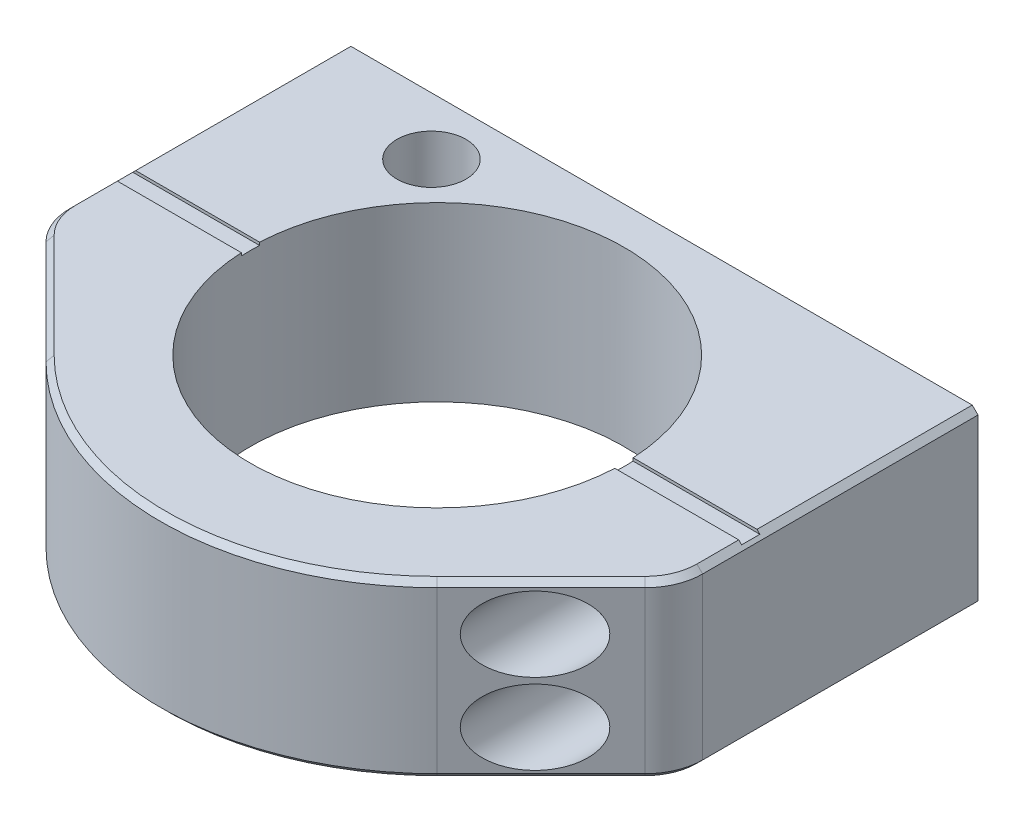
SolidWorks part; units mm, degrees
ref_plane "Front Plane" through (0, 0, 0) normal (0, 0, 1) x (1, 0, 0)
ref_plane "Top Plane" through (0, 0, 0) normal (0, 1, 0) x (1, 0, 0)
ref_plane "Right Plane" through (0, 0, 0) normal (1, 0, 0) x (0, 0, -1)
sketch "Sketch1" plane through (0, 0, 0) normal (0, 1, 0) x (1, 0, 0)
  line L0 (-34, -23) -> (-55, -2)
  line L2 (55, -2) -> (55, 50)
  line L3 (55, 50) -> (-55, 50)
  line L4 (-55, -2) -> (-55, 50)
  line L5 (34, -23) -> (55, -2)
  circle A0 centre (0, 11) radius 32.5
  arc A2 (-34, -23) -> (34, -23) centre (0, 11) ccw
  circle A4 centre (-30, 40) radius 6
  point P4 (55, -47)
  point P10 (-55, -47)
  dimension "D7" = 45
  dimension "D8" = 45
extrude "Boss-Extrude1" add sketch "Sketch1" along normal blind 30
sketch "Sketch2" plane through (0, 30, 0) normal (0, 1, 0) x (1, 0, 0)
  line L0 (-32.5, 11) -> (-55, 11)
  line L1 (-55, 50) -> (-55, -2) construction
  line L2 (-32.5, 11) -> (55, 11)
  line L3 (55, -2) -> (55, 50) construction
  line L4 (55, 11) -> (-55, 11) construction
  line L5 (55, 9.4125) -> (-55, 9.4125)
  line L6 (55, 12.5875) -> (-55, 12.5875)
  circle A0 centre (0, 11) radius 32.5 construction
  arc A1 (55, 9.4125) -> (55, 12.5875) centre (55, 11) ccw
  arc A2 (-55, 12.5875) -> (-55, 9.4125) centre (-55, 11) ccw
  point P11 (0, 11)
  line M1 (-55, 50) -> (-55, -2)
  line M5 (55, -2) -> (55, 50)
  circle M7 centre (0, 11) radius 32.5
  dimension "D1" = 3.175
  dimension "D2" = 110
extrude "Cut-Extrude1" cut sketch "Sketch2" against normal blind 0.5 contours L5 L0 M7 M1 | L6 L0 M7 M1 | L5 L2 M5 M7 | L6 L2 M5 M7 region at (-43.7435, 30, -10.206) region at (-43.7435, 30, -11.794) region at (43.7435, 30, -11.794) region at (43.7435, 30, -10.206)
sketch "Sketch3" plane through (0, 0, -50) normal (0, 0, -1) x (-1, 0, 0)
  circle A0 centre (42.5, 8) radius 4.5
  circle A1 centre (-42.5, 8) radius 4.5
  circle A2 centre (-42.5, 22) radius 4.5
  circle A3 centre (42.5, 22) radius 4.5
  dimension "D1" = 2
  dimension "D2" = 2
extrude "Cut-Extrude2" cut sketch "Sketch3" against normal through all
ref_plane "Plane1" through (0, 0, 10) normal (0, 0, -1) x (-1, 0, 0)
sketch "Sketch4" plane through (0, 0, 10) normal (0, 0, -1) x (-1, 0, 0)
  circle A0 centre (-42.5, 22) radius 6.5
  circle A1 centre (-42.5, 8) radius 6.5
  circle A2 centre (42.5, 8) radius 6.5
  circle A3 centre (42.5, 22) radius 6.5
extrude "Cut-Extrude3" cut sketch "Sketch4" against normal blind 25 and the other way blind 10
fillet "Fillet1" radius 10 2 edges at (-55, 15, 2) (55, 15, 2)
chamfer "Chamfer1" distance 1 angle 45 7 edges at (-55, 30, -5.7773) (-43.0355, 30, 13.9645) (0, 30, 37.0833) (43.0355, 30, 13.9645) (55, 30, -31.2937) (-54.2388, 30, 1.6847) (54.2388, 30, 1.6847)
chamfer "Chamfer2" distance 1 angle 45 7 edges at (55, 0, -26.0711) (43.0355, 0, 13.9645) (0, 0, 37.0833) (-43.0355, 0, 13.9645) (-55, 0, -26.0711) (54.2388, 0, 1.6847) (-54.2388, 0, 1.6847)
sketch "Sketch5" plane through (0, 30, 0) normal (0, 1, 0) x (1, 0, 0)
  line L0 (-55, 50) -> (-54, 50) construction
  line L1 (54, 50) -> (-54, 50) construction
  line L2 (54, 50) -> (55, 50) construction
  line L3 (55, 50) -> (55, 2.1421) construction
  line L4 (52.0711, -4.9289) -> (34, -23) construction
  line L5 (-34, -23) -> (-52.0711, -4.9289) construction
  line L6 (-55, 2.1421) -> (-55, 50) construction
  line L7 (-55, 50) -> (-54, 50)
  line L8 (54, 50) -> (-54, 50)
  line L9 (54, 50) -> (55, 50)
  line L10 (55, 50) -> (55, 2.1421)
  line L11 (52.0711, -4.9289) -> (34, -23)
  line L12 (-34, -23) -> (-52.0711, -4.9289)
  line L13 (-55, 2.1421) -> (-55, 50)
  arc A0 (52.0711, -4.9289) -> (55, 2.1421) centre (45, 2.1421) ccw construction
  arc A1 (-34, -23) -> (34, -23) centre (0, 11) ccw construction
  arc A2 (-55, 2.1421) -> (-52.0711, -4.9289) centre (-45, 2.1421) ccw construction
  arc A3 (52.0711, -4.9289) -> (55, 2.1421) centre (45, 2.1421) ccw
  arc A4 (-34, -23) -> (34, -23) centre (0, 11) ccw
  arc A5 (-55, 2.1421) -> (-52.0711, -4.9289) centre (-45, 2.1421) ccw
